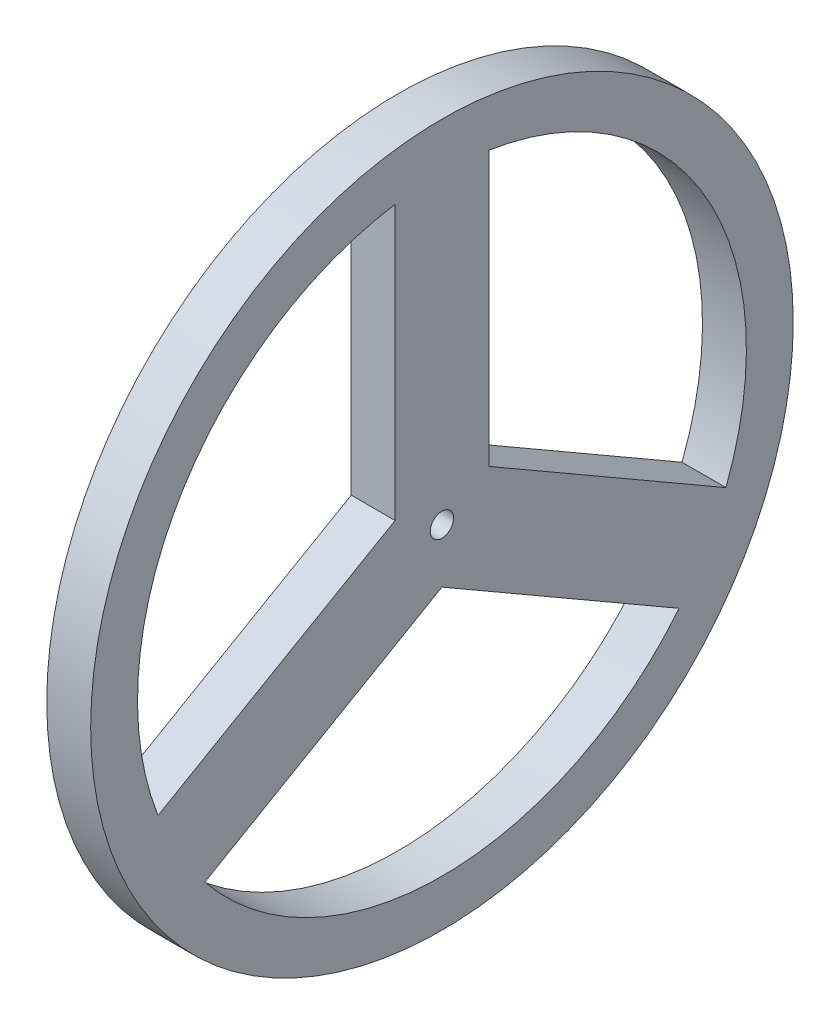
SolidWorks part; units mm, degrees
ref_plane "Front Plane" through (0, 0, 0) normal (0, 0, 1) x (1, 0, 0)
ref_plane "Top Plane" through (0, 0, 0) normal (0, 1, 0) x (1, 0, 0)
ref_plane "Right Plane" through (0, 0, 0) normal (1, 0, 0) x (0, 0, -1)
sketch "Sketch2" plane through (0, 0, 0) normal (1, 0, 0) x (0, 0, -1)
  line L0 (0, 33.02) -> (0, 0) construction
  line L1 (0, 0) -> (28.5962, -16.51) construction
  line L2 (0, 0) -> (-28.5962, -16.51) construction
  line L3 (-2.54, -4.3994) -> (26.0562, -20.9094)
  line L4 (-2.54, 4.3994) -> (-31.1362, -12.1106)
  line L5 (-5.08, 33.02) -> (-5.08, 0)
  line L6 (2.54, 4.3994) -> (31.1362, -12.1106)
  line L7 (2.54, -4.3994) -> (-26.0562, -20.9094)
  line L8 (5.08, 33.02) -> (5.08, 0)
  circle A0 centre (0, 0) radius 38.1
  circle A1 centre (0, 0) radius 33.02
  circle A2 centre (0, 0) radius 5.08
  circle A3 centre (0, 0) radius 1.27
  dimension "D1" = 76.2
  dimension "D3" = 10.16
  dimension "D4" = 2.54
  dimension "D6" = 120
  dimension "D5" = 120
  dimension "D7" = 5.08
  dimension "D2" = 5.08
  dimension "D8" = 5.08
extrude "Boss-Extrude5" add sketch "Sketch2" along normal blind 4.7625 contours A0
extrude "Cut-Extrude3" cut sketch "Sketch2<3>" along direction (1, 0, 0) on the side of the normal through all contours L7 A1 L3 | L5 A1 L4 | L6 A1 L8 | A3 region at (0, -21.1007, 0) region at (0, 10.5503, 18.2737) region at (0, 10.5503, -18.2737) region at (0, 0, 0)
sketch "Sketch2<3>" plane through (0, 0, 0) normal (1, 0, 0) x (0, 0, -1) same geometry as "Sketch2"
